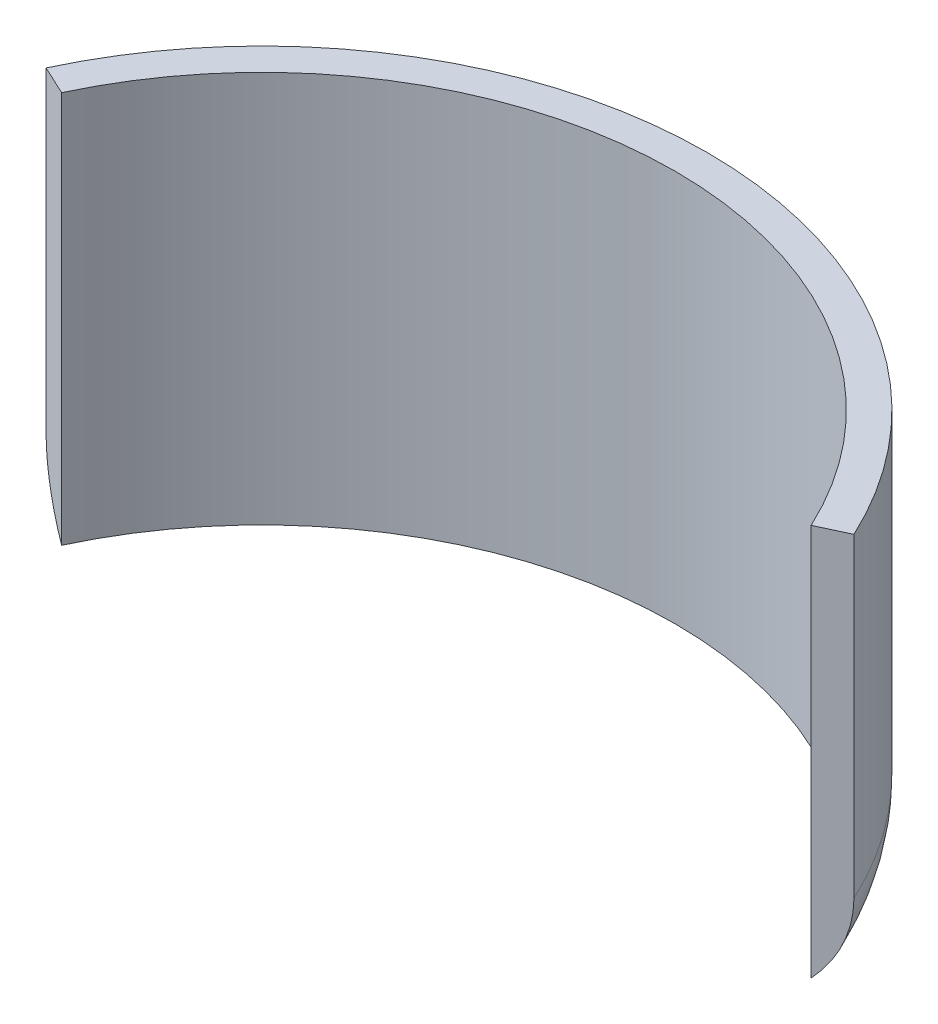
SolidWorks part; units mm, degrees
ref_plane "Front Plane" through (0, 0, 0) normal (0, 0, 1) x (1, 0, 0)
ref_plane "Top Plane" through (0, 0, 0) normal (0, 1, 0) x (1, 0, 0)
ref_plane "Right Plane" through (0, 0, 0) normal (1, 0, 0) x (0, 0, -1)
sketch "Sketch2" plane through (0, 0, 0) normal (1, 0, 0) x (0, 0, -1)
  line L0 (-40, 51.0988) -> (-40, -18.25) construction
  line L1 (-1.5, 18.25) -> (1.5, 18.25)
  line L2 (-1.5, 18.25) -> (-1.5, -18.25)
  line L3 (-1.5, -18.25) -> (1.5, -18.25)
  line L4 (1.5, 18.25) -> (1.5, -18.25)
  line L5 (-1.5, 18.25) -> (1.5, -18.25) construction
  line L6 (-1.5, -18.25) -> (1.5, 18.25) construction
  point P0 (0, 0)
  dimension "D1" = 36.5
  dimension "D2" = 3
  dimension "D3" = 40
revolve "Revolve1" add sketch "Sketch2" angle 65 about L0
fillet "Fillet1" radius 10 1 edges at (0, -18.25, -1.5)
